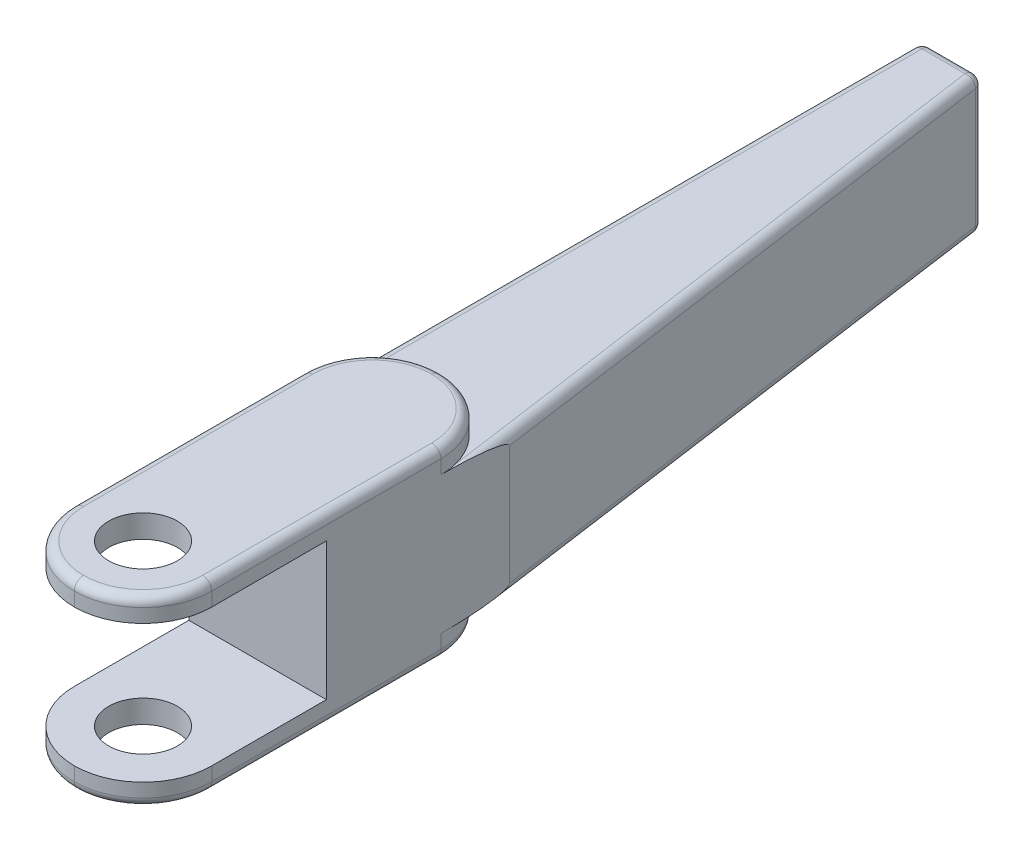
SolidWorks part; units mm, degrees
ref_plane "Front Plane" through (0, 0, 0) normal (0, 0, 1) x (1, 0, 0)
ref_plane "Top Plane" through (0, 0, 0) normal (0, 1, 0) x (1, 0, 0)
ref_plane "Right Plane" through (0, 0, 0) normal (1, 0, 0) x (0, 0, -1)
sketch "Sketch1" plane through (0, 0, 0) normal (0, 0, 1) x (1, 0, 0)
  line L1 (-15, 15) -> (15, 15)
  line L2 (-15, 15) -> (-15, -15)
  line L3 (-15, -15) -> (15, -15)
  line L4 (15, 15) -> (15, -15)
  line L5 (-15, 15) -> (15, -15) construction
  line L6 (-15, -15) -> (15, 15) construction
  point P0 (0, 0)
  dimension "D1" = 30
  dimension "D2" = 30
extrude "Boss-Extrude1" add sketch "Sketch1" along normal blind 160
sketch "Sketch2" plane through (0, 0, 160) normal (0, 0, 1) x (1, 0, 0)
  line L0 (15, 15) -> (-15, 15) construction
  line L1 (-15, 20) -> (15, 20)
  line L2 (-15, 20) -> (-15, -20)
  line L3 (-15, -20) -> (15, -20)
  line L4 (15, 20) -> (15, -20)
  line L5 (-15, 20) -> (15, -20) construction
  line L6 (-15, -20) -> (15, 20) construction
  point P0 (0, 0)
  line M2 (15, 15) -> (-15, 15)
  line M4 (-15, -15) -> (15, -15)
  dimension "D1" = 40
extrude "Boss-Extrude2" add sketch "Sketch2" against normal mid plane 80 contours L4 L1 L2 M2 | L4 L2 L3 M4 region at (0, 17.5, 160) region at (0, -17.5, 160)
fillet "Fillet1" radius 15 8 edges at (15, -17.5, 120) (-15, -17.5, 120) (-15, -17.5, 200) (15, -17.5, 200) (-15, 17.5, 120) (15, 17.5, 120) (-15, 17.5, 200) (15, 17.5, 200)
sketch "Sketch7" plane through (0, -20, 0) normal (0, -1, 0) x (1, 0, 0)
  circle A0 centre (0, 185) radius 7.5
  dimension "D1" = 15
extrude "Cut-Extrude1" cut sketch "Sketch7" against normal up to surface (40 mm away) up to face at (0, 20, 160)
chamfer "Chamfer1" distance 120 angle 8 1 edges at (15, 0, 0) first distance on face at (15, 0, 133.3333)
fillet "Fillet2" radius 2 20 edges at (15, 20, 160) (10.6066, 20, 195.6066) (-10.6066, 20, 195.6066) (-15, 20, 160) (-10.6066, 20, 124.3934) (10.6066, 20, 124.3934) (-15, -20, 160) (-10.6066, -20, 195.6066) (10.6066, -20, 195.6066) (15, -20, 160) (10.6066, -20, 124.3934) (-10.6066, -20, 124.3934) (-8.4325, 15, 0) (-15, 0, 0) (-8.4325, -15, 0) (-1.8649, 0, 0) (-15, 15, 67.5) (-15, -15, 67.5) (6.5675, 15, 60) (6.5675, -15, 60)
